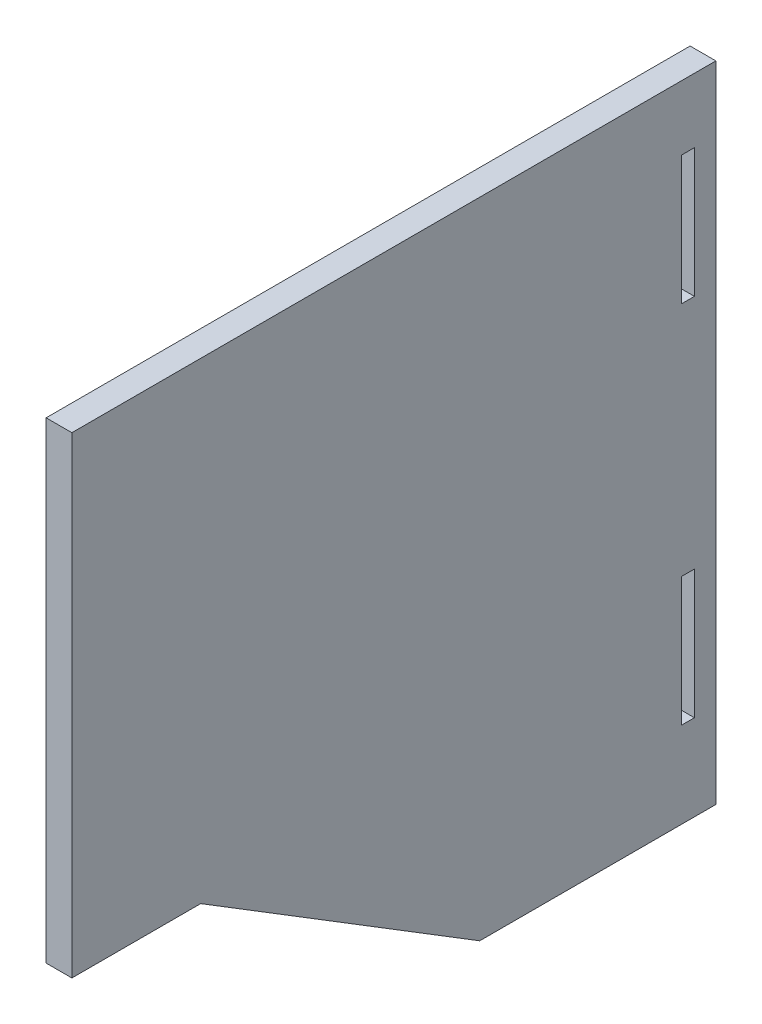
SolidWorks part; units mm, degrees
ref_plane "Front Plane" through (0, 0, 0) normal (0, 0, 1) x (1, 0, 0)
ref_plane "Top Plane" through (0, 0, 0) normal (0, 1, 0) x (1, 0, 0)
ref_plane "Right Plane" through (0, 0, 0) normal (1, 0, 0) x (0, 0, -1)
sketch "Sketch1" plane through (0, 0, 0) normal (0, 1, 0) x (1, 0, 0)
  line L1 (-50, -75) -> (50, -75)
  line L2 (-50, -75) -> (-50, 75)
  line L3 (-50, 75) -> (50, 75)
  line L4 (50, -75) -> (50, 75)
  line L5 (-50, -75) -> (50, 75) construction
  line L6 (-50, 75) -> (50, -75) construction
  point P0 (0, 0)
  dimension "D1" = 100
  dimension "D2" = 150
extrude "Boss-Extrude1" add sketch "Sketch1" along normal blind 150
sketch "Sketch13" plane through (50, 0, 0) normal (1, 0, 0) x (0, 0, -1)
  line L0 (-45, 40) -> (20, 0)
  line L1 (-75, 0) -> (-45, 0)
  line L2 (-75, 0) -> (-75, 40)
  line L3 (-75, 40) -> (-45, 40)
  line L5 (-75, 0) -> (75, 0) construction
  line L8 (-45, 0) -> (20, 0)
  dimension "D1" = 30
  dimension "D2" = 40
  dimension "D3" = 55
extrude "Cut-Extrude7" cut sketch "Sketch13" against normal up to next
shell "Shell1" thickness 5 removed face at (0, 150, 0)
sketch "Sketch3" plane through (0, 0, 0) normal (0, -1, 0) x (1, 0, 0)
  line L1 (50, 45) -> (50, 75) construction
  circle A0 centre (0, 60) radius 4
  circle A1 centre (-5, 50) radius 1.5
  circle A2 centre (5, 50) radius 1.5
  dimension "D3" = 8
  dimension "D4" = 3
  dimension "D5" = 10
  dimension "D7" = 10
  dimension "D8" = 5
  dimension "D1" = 60
  dimension "D2" = 50
extrude "Cut-Extrude2" cut sketch "Sketch3" against normal up to next
sketch "Sketch5" plane through (0, 0, 75) normal (0, 0, 1) x (1, 0, 0)
  line L0 (50, 150) -> (50, 40) construction
  line L1 (-25, 50) -> (25, 50)
  line L2 (-25, 50) -> (-25, 97)
  line L3 (-25, 97) -> (25, 97)
  line L4 (25, 50) -> (25, 97)
  line L5 (-25, 50) -> (25, 97) construction
  line L6 (-25, 97) -> (25, 50) construction
  line L7 (-50, 150) -> (50, 150) construction
  point P0 (0, 73.5)
  dimension "D1" = 50
  dimension "D2" = 47
  dimension "D3" = 50
  dimension "D4" = 76.5
sketch "Sketch8" plane through (0, 0, 75) normal (0, 0, 1) x (1, 0, 0)
  line L0 (-50, 150) -> (-50, 40) construction
  line L1 (-25, 100) -> (25, 100)
  line L2 (-25, 100) -> (-25, 139)
  line L3 (-25, 139) -> (25, 139)
  line L4 (25, 100) -> (25, 139)
  line L5 (-25, 100) -> (25, 139) construction
  line L6 (-25, 139) -> (25, 100) construction
  line L7 (-50, 150) -> (50, 150) construction
  point P0 (0, 119.5)
  dimension "D1" = 50
  dimension "D2" = 39
  dimension "D3" = 50
  dimension "D4" = 50
extrude "Cut-Extrude3" cut sketch "Sketch8" against normal up to next
sketch "Sketch18" plane through (0, 0, 70) normal (0, 0, -1) x (-1, 0, 0)
  line L0 (-25, 139) -> (25, 139) construction
  line L1 (30, 99) -> (-26, 99)
  line L2 (30, 99) -> (30, 140)
  line L3 (30, 140) -> (-26, 140)
  line L4 (-26, 99) -> (-26, 140)
  line L6 (-25, 100) -> (-25, 139) construction
  line L7 (25, 139) -> (25, 100) construction
  dimension "D1" = 1
  dimension "D2" = 41
  dimension "D3" = 1
  dimension "D4" = 5
extrude "Cut-Extrude9" cut sketch "Sketch18" against normal blind 2
sketch "Sketch21" plane through (0, 45, 0) normal (0, 1, 0) x (1, 0, 0)
  line L1 (9, -52.5) -> (-9, -52.5)
  line L2 (9, -52.5) -> (9, -37.5)
  line L3 (9, -37.5) -> (-9, -37.5)
  line L4 (-9, -52.5) -> (-9, -37.5)
  circle A0 centre (5, -50) radius 1.5 construction
  circle A1 centre (-5, -50) radius 1.5 construction
  dimension "D3" = 4
  dimension "D1" = 4
  dimension "D2" = 2.5
  dimension "D4" = 15
extrude "Cut-Extrude11" cut sketch "Sketch21" against normal blind 2.5
sketch "Sketch22" plane through (-45, 0, 0) normal (1, 0, 0) x (0, 0, -1)
  line L0 (70, 150) -> (-70, 150) construction
  line L5 (70, 150) -> (70, 5) construction
  line L7 (-43.5848, 45) -> (21.4152, 5) construction
  line L8 (10, 150) -> (10, 12.0247)
  line L11 (10, 150) -> (5, 150)
  line L14 (5, 150) -> (5, 15.1017)
  line L15 (5, 15.1017) -> (10, 12.0247)
  dimension "D1" = 60
  dimension "D3" = 5
extrude "Boss-Extrude6" add sketch "Sketch22" along normal blind 5
mirror "Mirror2" about plane through (0, 0, 0) normal (1, 0, 0) of "Boss-Extrude6"
sketch "Sketch23" plane through (-45, 0, 0) normal (1, 0, 0) x (0, 0, -1)
  line L0 (16, 150) -> (21, 150)
  line L1 (70, 150) -> (10, 150) construction
  line L3 (21, 150) -> (21, 5.2555)
  line L4 (21, 5.2555) -> (16, 8.3324)
  line L6 (10, 12.0247) -> (10, 150) construction
  line L7 (16, 150) -> (16, 8.3324)
  line L8 (10, 12.0247) -> (21.4152, 5) construction
  dimension "D1" = 6
  dimension "D2" = 5
extrude "Boss-Extrude7" add sketch "Sketch23" along normal up to next
sketch "Sketch35" plane through (-50, 0, 0) normal (-1, 0, 0) x (0, 0, 1)
  line L0 (-75, 150) -> (75, 150)
  line L1 (75, 150) -> (75, 40)
  line L2 (75, 40) -> (45, 40)
  line L3 (45, 40) -> (-20, 0)
  line L4 (-20, 0) -> (-75, 0)
  line L5 (-75, 150) -> (-75, 0)
extrude "Boss-Extrude8" add sketch "Sketch35" along normal blind 1
sketch "Sketch24" plane through (-45, 0, 0) normal (1, 0, 0) x (0, 0, -1)
  line L0 (70, 150) -> (70, 5) construction
  line L1 (70, 135) -> (67, 135)
  line L2 (70, 135) -> (70, 105)
  line L3 (70, 105) -> (67, 105)
  line L4 (67, 135) -> (67, 105)
  line L5 (70, 150) -> (21, 150) construction
  line L6 (70, 5) -> (21.4152, 5) construction
  line L7 (70, 20) -> (67, 20)
  line L8 (70, 20) -> (70, 50)
  line L9 (70, 50) -> (67, 50)
  line L10 (67, 20) -> (67, 50)
  dimension "D1" = 15
  dimension "D2" = 30
  dimension "D3" = 3
  dimension "D4" = 15
extrude "Cut-Extrude12" cut sketch "Sketch24" against normal through all both and the other way through all
sketch "Sketch30" plane through (0, 0, -75) normal (0, 0, -1) x (-1, 0, 0)
  text T0 "IBE VAN DE VEIRE\r\nSTEF GIELEN" font "Comic Sans MS" height 5
extrude "Cut-Extrude16" cut sketch "Sketch30" against normal blind 1
sketch "Sketch33" plane through (0, 150, 0) normal (0, 1, 0) x (1, 0, 0)
  line L1 (-45, 5) -> (45, 5)
  line L2 (-45, 5) -> (-45, 21)
  line L3 (-45, 21) -> (45, 21)
  line L4 (45, 5) -> (45, 21)
extrude "Cut-Extrude18" cut sketch "Sketch33" against normal blind 40
sketch "Sketch34" plane through (0, 150, 0) normal (0, 1, 0) x (1, 0, 0)
  line L0 (50, 75) -> (-51, 75) construction
  line L1 (-45, 75) -> (50, 75)
  line L2 (-45, 75) -> (-45, -75)
  line L3 (-45, -75) -> (50, -75)
  line L4 (50, 75) -> (50, -75)
extrude "Cut-Extrude19" cut sketch "Sketch34" against normal through all both and the other way through all
